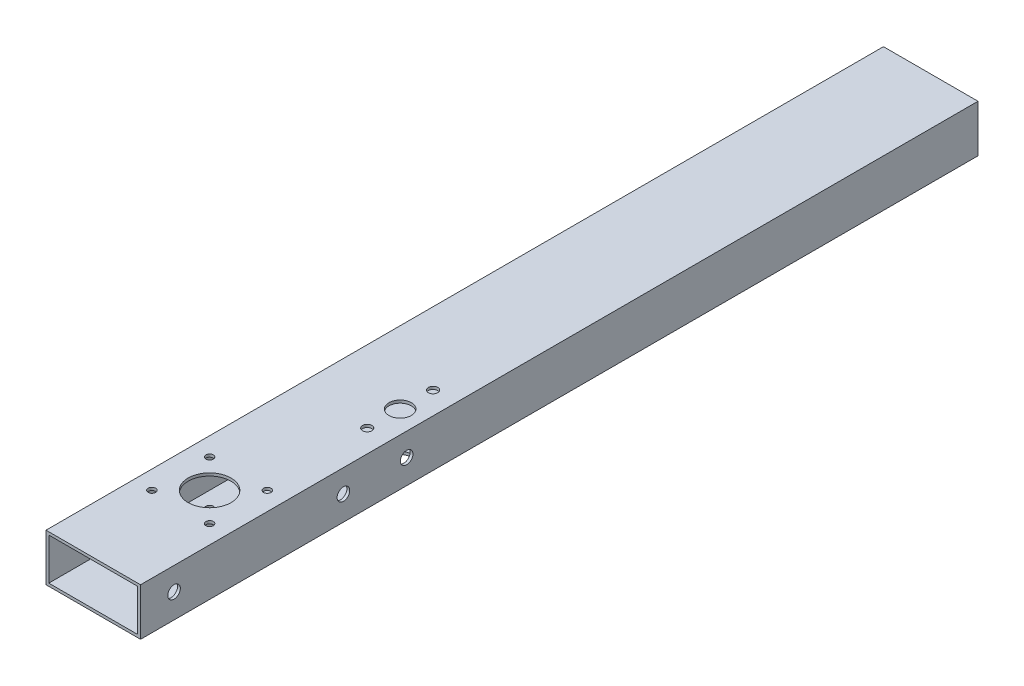
SolidWorks part; units mm, degrees
material "AISI 1015 Acero estirado en frío (SS)"
ref_plane "Alzado" through (0, 0, 0) normal (0, 0, 1) x (1, 0, 0)
ref_plane "Planta" through (0, 0, 0) normal (0, 1, 0) x (1, 0, 0)
ref_plane "Vista lateral" through (0, 0, 0) normal (1, 0, 0) x (0, 0, -1)
sketch "Croquis1" plane through (0, 0, 0) normal (0, 0, 1) x (1, 0, 0)
  line L0 (-23.9, -11.2) -> (-23.9, 11.2)
  line L1 (-25.4, -12.7) -> (25.4, -12.7)
  line L2 (-25.4, -12.7) -> (-25.4, 12.7)
  line L3 (-25.4, 12.7) -> (25.4, 12.7)
  line L4 (25.4, -12.7) -> (25.4, 12.7)
  line L5 (-25.4, -12.7) -> (25.4, 12.7) construction
  line L6 (-25.4, 12.7) -> (25.4, -12.7) construction
  line L7 (-23.9, 11.2) -> (23.9, 11.2)
  line L8 (23.9, -11.2) -> (23.9, 11.2)
  line L9 (-23.9, -11.2) -> (23.9, -11.2)
  point P0 (0, 0)
  dimension "D1" = 25.4
  dimension "D2" = 50.8
  dimension "D3" = 1.5
extrude "Saliente-Extruir1" add sketch "Croquis1" along normal blind 450
ref_plane "Plano1" through (0, -12.7, 0) normal (0, -1, 0) x (-1, 0, 0)
sketch "Croquis2" plane through (0, -12.7, 0) normal (0, -1, 0) x (-1, 0, 0)
  line L0 (0, -450) -> (0, -222.1085) construction
  line L1 (25.4, -450) -> (-25.4, -450) construction
  line L2 (25.4, -387.5) -> (-25.4, -387.5) construction
  line L3 (25.4, -450) -> (25.4, 0) construction
  line L4 (-25.4, -450) -> (-25.4, 0) construction
  circle A0 centre (0, -387.5) radius 11.5
  circle A1 centre (15.5, -403) radius 2
  circle A2 centre (-15.5, -403) radius 2
  circle A3 centre (-15.5, -372) radius 2
  circle A4 centre (15.5, -372) radius 2
  dimension "D3" = 23
  dimension "D4" = 4
  dimension "D1" = 62.5
  dimension "D2" = 15.5
  dimension "D5" = 15.5
extrude "Cortar-Extruir1" cut sketch "Croquis2" against normal blind 26
hole_wizard "Taladro de margen para 1/41" positions "Croquis3" profile "Croquis4" hole size "1/4" standard "Ansi Inch" end condition through all
sketch "Croquis3" plane through (-25.4, 197.8886, 162.9891) normal (-1, 0, 0) x (0, -1, 0)
  point P0 (197.4886, 269.0109)
  point P3 (197.4886, 178.0109)
  point P6 (197.4886, 144.0109)
  point P9 (572.8886, 144.0109)
  point P12 (572.8886, 178.0109)
  point P15 (572.8886, 269.0109)
  point P19 (197.4886, 269.0109)
  point P21 (197.4886, 144.0109)
sketch "Croquis4" plane through (-25.4, 0.4, 432) normal (0, 1, 0) x (0, 0, 1)
  line L0 (0, 0) -> (0, 50.8)
  line L1 (0, 50.8) -> (3.3782, 50.8)
  line L2 (3.3782, 50.8) -> (3.3782, 0)
  line L3 (3.3782, 0) -> (0, 0)
  line L4 (0, -6.35) -> (0, 107.95) construction
  dimension "Diámetro de taladro hasta el siguiente" = 6.7564
  dimension "Profundidad de taladro hasta el siguiente" = 50.8
sketch "Croquis5" plane through (0, -12.7, 0) normal (0, -1, 0) x (1, 0, 0)
  line L0 (-25.4, 298.5) -> (25.4, 298.5) construction
  line L1 (-25.4, 450) -> (-25.4, 0) construction
  line L2 (25.4, 450) -> (25.4, 0) construction
  line L3 (13.4, 280.8) -> (13.4, 316.2) construction
  circle A0 centre (13.4, 298.5) radius 6
  circle A1 centre (13.4, 316.2) radius 2.5
  circle A2 centre (13.4, 280.8) radius 2.5
  point P6 (0, 387.5)
  point P11 (13.4, 298.5)
  dimension "D2" = 12
  dimension "D5" = 5
  dimension "D1" = 89
  dimension "D3" = 35.4
  dimension "D4" = 12
extrude "Cortar-Extruir2" cut sketch "Croquis5" against normal up to surface (25.4 mm away) up to face at (-15.5, 12.7, 370)
